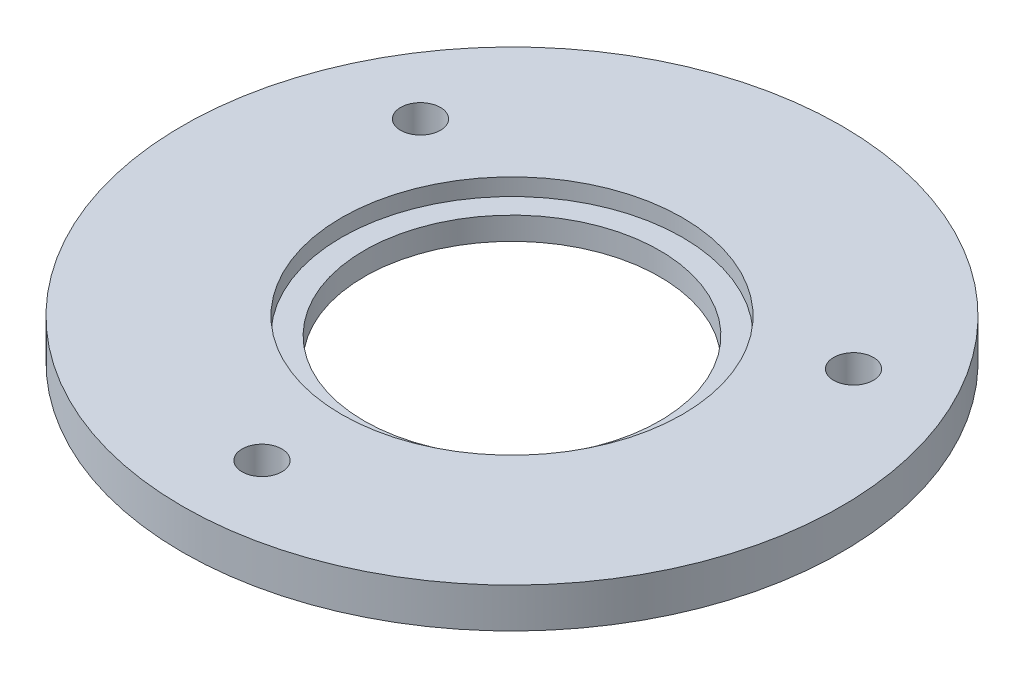
SolidWorks part; units mm, degrees
ref_plane "Front Plane" through (0, 0, 0) normal (0, 0, 1) x (1, 0, 0)
ref_plane "Top Plane" through (0, 0, 0) normal (0, 1, 0) x (1, 0, 0)
ref_plane "Right Plane" through (0, 0, 0) normal (1, 0, 0) x (0, 0, -1)
sketch "Sketch1" plane through (0, 0, 0) normal (0, 1, 0) x (1, 0, 0)
  circle A0 centre (0, 0) radius 15
  circle A1 centre (0, 0) radius 13
  circle A2 centre (0, 0) radius 29
  dimension "D1" = 30
  dimension "D2" = 2
  dimension "D3" = 14
extrude "Boss-Extrude1" add sketch "Sketch1" along normal blind 2 contours A0 A1 region at (-14.5757, 0, 0)
extrude "Boss-Extrude3" add sketch "Sketch1<5>" along normal offset from surface (3.5 mm away) 1.5 contours A2 A0 region at (-28.1798, 0, 0) up to face at (0, 2, 13) offset beyond the face yes
sketch "Sketch1<5>" plane through (0, 0, 0) normal (0, 1, 0) x (1, 0, 0) same geometry as "Sketch1"
sketch "Sketch2" plane through (0, 3.5, 0) normal (0, 1, 0) x (1, 0, 0)
  line L0 (0, -15) -> (0, -29) construction
  circle A0 centre (0, 0) radius 15 construction
  circle A1 centre (0, 0) radius 29 construction
  circle A2 centre (0, -22) radius 1.75
  dimension "D1" = 3.5
extrude "Cut-Extrude1" cut sketch "Sketch2" against normal blind 4.5
pattern_circular "CirPattern1" count 3 over 360 about axis through (0, 2, 0) along (0, -1, 0) of "Cut-Extrude1"
